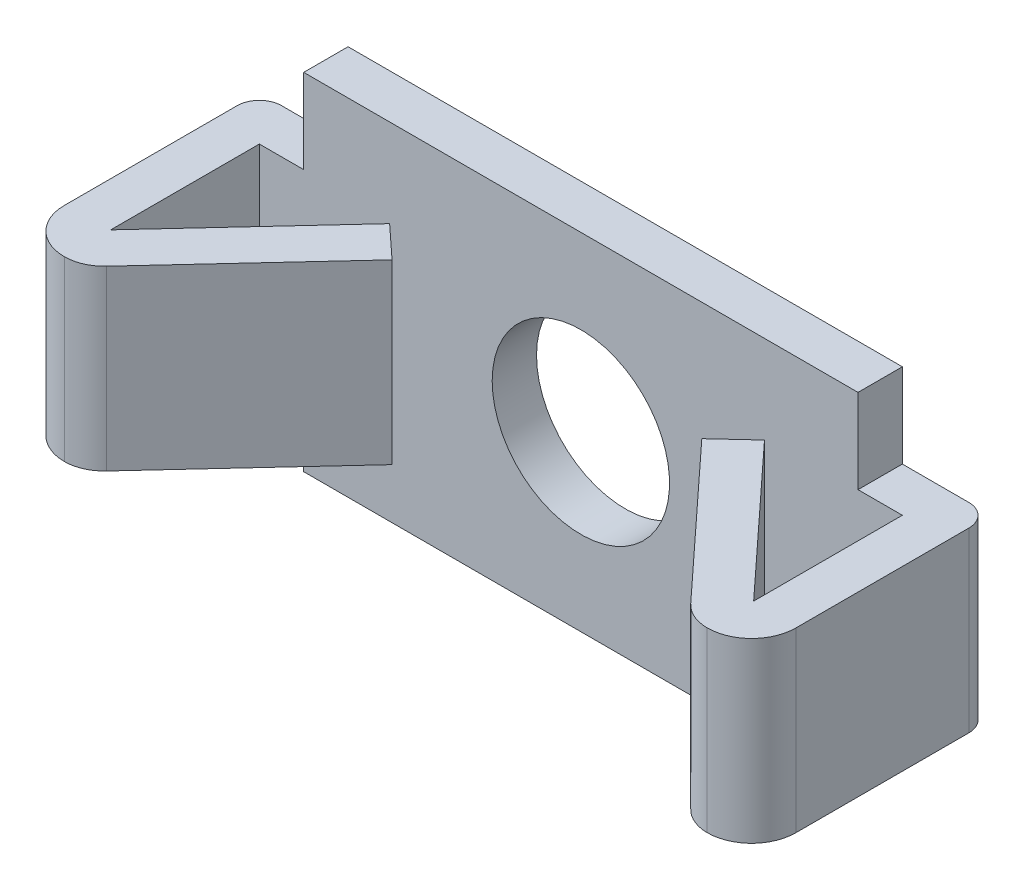
SolidWorks part; units mm, degrees
ref_plane "前视基准面" through (0, 0, 0) normal (0, 0, 1) x (1, 0, 0)
ref_plane "上视基准面" through (0, 0, 0) normal (0, 1, 0) x (1, 0, 0)
ref_plane "右视基准面" through (0, 0, 0) normal (1, 0, 0) x (0, 0, -1)
sketch "草图1" plane through (0, 0, 0) normal (0, 0, 1) x (1, 0, 0)
  line L1 (-16.5, -7.8) -> (16.5, -7.8)
  line L2 (-16.5, -7.8) -> (-16.5, 7.8)
  line L3 (-16.5, 7.8) -> (16.5, 7.8)
  line L4 (16.5, -7.8) -> (16.5, 7.8)
  line L5 (-16.5, -7.8) -> (16.5, 7.8) construction
  line L6 (-16.5, 7.8) -> (16.5, -7.8) construction
  point P0 (0, 0)
  dimension "D1" = 33
  dimension "D2" = 15.6
extrude "凸台-拉伸1" add sketch "草图1" along normal blind 2
sketch "草图2" plane through (0, 0, 2) normal (0, 0, 1) x (1, 0, 0)
  line L0 (0, 7.8) -> (0, -7.8) construction
  line L1 (16.5, 7.8) -> (-16.5, 7.8) construction
  line L2 (-16.5, -7.8) -> (16.5, -7.8) construction
  line L3 (-12.5, 7.8) -> (-12.5, 4)
  line L4 (12.5, 7.8) -> (12.5, 4)
  line L5 (-12.5, 0) -> (-16.5, 0) construction
  line L6 (-16.5, 7.8) -> (-16.5, -7.8) construction
  line L7 (12.5, 0) -> (16.5, 0) construction
  line L8 (16.5, -7.8) -> (16.5, 7.8) construction
  line L9 (-12.5, 4) -> (-16.5, 4)
  line L10 (-12.5, -4) -> (-16.5, -4)
  line L11 (12.5, 4) -> (16.5, 4)
  line L12 (12.5, -4) -> (16.5, -4)
  line L13 (-12.5, -4) -> (-12.5, -7.8)
  line L14 (12.5, -4) -> (12.5, -7.8)
  line L15 (-12.5, 7.8) -> (-12.5, -7.8) construction
  line L16 (-16.5, 4) -> (-16.5, 7.8)
  line L17 (12.5, 7.8) -> (12.5, -7.8) construction
  line L18 (-16.5, 7.8) -> (-12.5, 7.8)
  line L19 (-16.5, -4) -> (-16.5, -7.8)
  line L20 (-16.5, -7.8) -> (-12.5, -7.8)
  line L21 (12.5, 7.8) -> (16.5, 7.8)
  line L22 (16.5, 7.8) -> (16.5, 4)
  line L23 (12.5, -7.8) -> (16.5, -7.8)
  line L24 (16.5, -7.8) -> (16.5, -4)
  dimension "D1" = 12.5
  dimension "D2" = 12.5
  dimension "D3" = 4
  dimension "D4" = 4
  dimension "D5" = 4
  dimension "D6" = 4
extrude "切除-拉伸1" cut sketch "草图2" against normal through all
sketch "草图4" plane through (-16.5, 0, 0) normal (-1, 0, 0) x (0, 0, 1)
  line L0 (0, 4) -> (10.8, 4)
  line L1 (10.8, 4) -> (10.8, -4)
  line L2 (10.8, -4) -> (0, -4)
  line L3 (0, -4) -> (0, 4)
extrude "凸台-拉伸2" add sketch "草图4" against normal blind 2
sketch "草图5" plane through (0, 4, 0) normal (0, 1, 0) x (1, 0, 0)
  line L0 (-14.5, -10.8) -> (-14.5, -2) construction
  line L1 (-8.4533, -2.1721) -> (-14.5, -8.7072)
  line L2 (-6.9853, -3.5304) -> (-13.1722, -10.2169)
  line L3 (-14.5, -8.7072) -> (-14.5, -10.8)
  line L4 (-8.4533, -2.1721) -> (-6.9853, -3.5304)
  line L5 (-7.4232, -1.0588) -> (-14.6442, -8.863) construction
  line L7 (-5.9552, -2.4171) -> (-13.1762, -10.2213) construction
  arc A0 (-14.5, -10.8) -> (-13.1722, -10.2169) centre (-14.5, -8.9965) ccw
  dimension "D1" = 2
extrude "凸台-拉伸4" add sketch "草图5" against normal blind 8
sketch "草图6" plane through (0, 0, 0) normal (0, 0, -1) x (-1, 0, 0)
  circle A0 centre (0, 0) radius 4
  dimension "D1" = 8
extrude "切除-拉伸2" cut sketch "草图6" against normal through all
mirror "镜向2" about plane through (0, 0, 0) normal (1, 0, 0) of "凸台-拉伸2"
mirror "镜向3" about plane through (0, 0, 0) normal (1, 0, 0) of "凸台-拉伸4"
fillet "圆角1" radius 2 2 edges at (16.5, 0, 10.8) (-16.5, 0, 10.8)
fillet "圆角2" radius 1 2 edges at (16.5, 0, 0) (-16.5, 0, 0)
